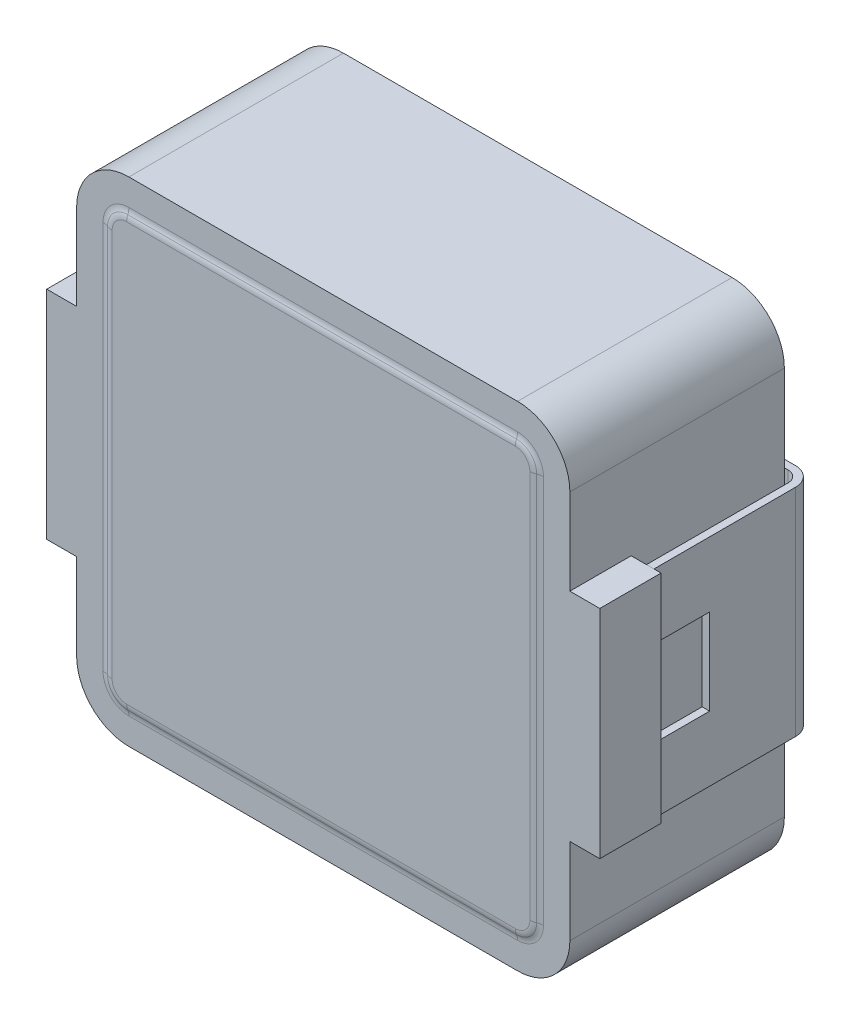
SolidWorks part; units mm, degrees
ref_plane "Front Plane" through (0, 0, 0) normal (0, 0, 1) x (1, 0, 0)
ref_plane "Top Plane" through (0, 0, 0) normal (0, 1, 0) x (1, 0, 0)
ref_plane "Right Plane" through (0, 0, 0) normal (1, 0, 0) x (0, 0, -1)
sketch "Sketch1" plane through (0, 0, 0) normal (0, 0, 1) x (1, 0, 0)
  line L1 (-3.3, 3.3) -> (3.3, 3.3)
  line L2 (-3.3, 3.3) -> (-3.3, -3.3)
  line L3 (-3.3, -3.3) -> (3.3, -3.3)
  line L4 (3.3, 3.3) -> (3.3, -3.3)
  line L5 (-3.3, 3.3) -> (3.3, -3.3) construction
  line L6 (-3.3, -3.3) -> (3.3, 3.3) construction
  point P0 (0, 0)
  dimension "D1" = 6.6
  dimension "D2" = 6.6
extrude "Boss-Extrude1" add sketch "Sketch1" along normal blind 2.9
sketch "Sketch6" plane through (0, 0, 2.9) normal (0, 0, 1) x (1, 0, 0)
  line L1 (-3.7, 1.45) -> (3.7, 1.45)
  line L2 (-3.7, 1.45) -> (-3.7, -1.45)
  line L3 (-3.7, -1.45) -> (3.7, -1.45)
  line L4 (3.7, 1.45) -> (3.7, -1.45)
  line L5 (-3.7, 1.45) -> (3.7, -1.45) construction
  line L6 (-3.7, -1.45) -> (3.7, 1.45) construction
  point P0 (0, 0)
  point P5 (0, 0)
  point P7 (-4.4417, -0.9688)
  dimension "D1" = 7.4
  dimension "D2" = 2.9
extrude "Boss-Extrude5" add sketch "Sketch6" against normal blind 0.85
fillet "Fillet1" radius 0.7 4 edges at (3.3, 3.3, 1.45) (-3.3, 3.3, 1.45) (3.3, -3.3, 1.45) (-3.3, -3.3, 1.45)
sketch "Sketch2" plane through (0, 0, 0) normal (0, 0, -1) x (-1, 0, 0)
  line L0 (3.3, 2.6) -> (3.3, -2.6) construction
  line L1 (3.3, -1.05) -> (2.4, -1.05)
  line L2 (3.3, -1.05) -> (3.3, 1.05)
  line L3 (3.3, 1.05) -> (2.4, 1.05)
  line L4 (2.4, -1.05) -> (2.4, 1.05)
  line L5 (3.3, -1.05) -> (2.4, 1.05) construction
  line L6 (3.3, 1.05) -> (2.4, -1.05) construction
  line L7 (-3.3, -2.6) -> (-3.3, 2.6) construction
  line L8 (-3.3, -1.05) -> (-2.4, -1.05)
  line L9 (-3.3, -1.05) -> (-3.3, 1.05)
  line L10 (-3.3, 1.05) -> (-2.4, 1.05)
  line L11 (-2.4, -1.05) -> (-2.4, 1.05)
  line L12 (-3.3, -1.05) -> (-2.4, 1.05) construction
  line L13 (-3.3, 1.05) -> (-2.4, -1.05) construction
  point P4 (2.85, 0)
  point P11 (-2.85, 0)
  point P14 (2.4, 0)
  point P16 (-2.4, 0)
  dimension "D1" = 0.9
  dimension "D2" = 2.1
extrude "Cut-Extrude1" cut sketch "Sketch2" against normal blind 0.05
sketch "Sketch3" plane through (0, 0, 0.05) normal (0, 0, -1) x (-1, 0, 0)
  line L0 (3.3, -1.05) -> (3.3, 1.05) construction
  line L1 (2.3, -1.445) -> (3.6, -1.445)
  line L2 (2.3, -1.445) -> (2.3, 1.445)
  line L3 (2.3, 1.445) -> (3.6, 1.445)
  line L4 (3.6, -1.445) -> (3.6, 1.445)
  line L5 (2.3, -1.445) -> (3.6, 1.445) construction
  line L6 (2.3, 1.445) -> (3.6, -1.445) construction
  point P4 (2.95, 0)
  dimension "D1" = 1.3
  dimension "D2" = 2.89
  dimension "D3" = 0.3
extrude "Boss-Extrude2" add sketch "Sketch3" along normal blind 0.15
sketch "Sketch4" plane through (0, 0, 0.05) normal (0, 0, 1) x (1, 0, 0)
  line L1 (-3.6, -1.445) -> (-3.3, -1.445)
  line L2 (-3.6, -1.445) -> (-3.6, 1.445)
  line L3 (-3.6, 1.445) -> (-3.3, 1.445)
  line L4 (-3.3, -1.445) -> (-3.3, 1.445)
  line L5 (-3.6, -1.445) -> (-3.3, 1.445) construction
  line L6 (-3.6, 1.445) -> (-3.3, -1.445) construction
  point P4 (-3.45, 0)
extrude "Boss-Extrude3" add sketch "Sketch4" along normal up to surface (2 mm away) up to face at (-3.5, 0, 2.05)
fillet "Fillet2" radius 0.25 1 edges at (-3.6, 0, -0.1)
sketch "Sketch5" plane through (0, 0, 0) normal (0, 0, -1) x (-1, 0, 0)
  line L0 (2.725, -2.7) -> (-2.725, -2.7)
  line L1 (-2.725, -2.7) -> (-2.725, -1.8)
  line L2 (-2.725, -1.8) -> (-1, -1.8)
  line L3 (-1, -1.8) -> (-1, 1.8)
  line L4 (-1, 1.8) -> (-2.725, 1.8)
  line L5 (-2.725, 1.8) -> (-2.725, 2.7)
  line L6 (-2.725, 2.7) -> (2.725, 2.7)
  line L7 (2.725, 2.7) -> (2.725, 1.8)
  line L8 (2.725, 1.8) -> (1, 1.8)
  line L9 (1, 1.8) -> (1, -1.8)
  line L10 (1, -1.8) -> (2.725, -1.8)
  line L11 (2.725, -1.8) -> (2.725, -2.7)
  line L12 (0, -0.4595) -> (0, 0.4595) construction
  line L13 (0.6641, 0) -> (-0.6641, 0) construction
  point P17 (-2.3702, 2.6558)
  point P18 (2.3753, 2.7459)
  point P19 (1.0462, 1.7848)
  dimension "D1" = 5.4
  dimension "D2" = 5.45
  dimension "D3" = 2
  dimension "D4" = 3.6
extrude "Boss-Extrude4" add sketch "Sketch5" along normal blind 0.1
fillet "Fillet3" radius 0.05 12 edges at (0, -2.7, -0.1) (2.725, -2.25, -0.1) (1.8625, -1.8, -0.1) (1, 0, -0.1) (1.8625, 1.8, -0.1) (2.725, 2.25, -0.1) (0, 2.7, -0.1) (-2.725, 2.25, -0.1) (-1.8625, 1.8, -0.1) (-1, 0, -0.1) (-1.8625, -1.8, -0.1) (-2.725, -2.25, -0.1)
fillet "Fillet4" radius 0.05 12 edges at (-1.8625, 1.8, 0) (-2.725, 2.25, 0) (0, 2.7, 0) (2.725, 2.25, 0) (1.8625, 1.8, 0) (1, 0, 0) (1.8625, -1.8, 0) (2.725, -2.25, 0) (0, -2.7, 0) (-1, 0, 0) (-2.725, -2.25, 0) (-1.8625, -1.8, 0)
sketch "Sketch8" plane through (0, 0, 0) normal (0, 0, -1) x (-1, 0, 0)
  line L0 (3.6, 1.445) -> (3.6, -1.445) construction
  line L1 (3.5, -1.445) -> (3.3, -1.445)
  line L2 (3.5, -1.445) -> (3.5, 1.445)
  line L3 (3.5, 1.445) -> (3.3, 1.445)
  line L4 (3.3, -1.445) -> (3.3, 1.445)
  line L5 (3.5, -1.445) -> (3.3, 1.445) construction
  line L6 (3.5, 1.445) -> (3.3, -1.445) construction
  point P4 (3.4, 0)
  point P5 (0, 0)
  point P7 (0, 0)
  dimension "D1" = 0.1
extrude "Cut-Extrude2" cut sketch "Sketch8" against normal up to surface (2.05 mm away) up to face at (-3.475, 0, 2.05)
fillet "Fillet5" radius 0.15 1 edges at (-3.5, 0, 0)
sketch "Sketch9" plane through (-3.6, 0, 0) normal (-1, 0, 0) x (0, 0, 1)
  line L0 (2.05, 1.445) -> (2.05, -1.445) construction
  line L1 (2.05, 0.575) -> (1.3, 0.575)
  line L2 (2.05, 0.575) -> (2.05, -0.575)
  line L3 (2.05, -0.575) -> (1.3, -0.575)
  line L4 (1.3, 0.575) -> (1.3, -0.575)
  line L5 (2.05, 0.575) -> (1.3, -0.575) construction
  line L6 (2.05, -0.575) -> (1.3, 0.575) construction
  point P4 (1.675, 0)
  point P7 (0, 0)
  dimension "D1" = 1.15
  dimension "D2" = 0.75
extrude "Cut-Extrude3" cut sketch "Sketch9" against normal up to surface (0.1 mm away) up to face at (-3.5, 0, 1.1)
mirror "Mirror2" about plane through (0, 0, 0) normal (1, 0, 0) of "Fillet5", "Boss-Extrude3", "Boss-Extrude2", "Fillet2", "Cut-Extrude2", "Cut-Extrude3"
sketch "Sketch10" plane through (0, 0, 2.9) normal (0, 0, 1) x (1, 0, 0)
  line L0 (2.6, 3.3) -> (-2.6, 3.3) construction
  line L1 (-2.6, 2.9) -> (2.6, 2.9)
  line L2 (-2.9, 2.6) -> (-2.9, -2.6)
  line L3 (-2.6, -2.9) -> (2.6, -2.9)
  line L4 (2.9, 2.6) -> (2.9, -2.6)
  line L5 (-2.6661, -2.19) -> (3.6721, 3.0164) construction
  line L6 (4.5434, -2.7178) -> (-1.7923, 1.0721) construction
  line L8 (-4.497, 5.4132) -> (5.503, 5.4132)
  line L9 (-4.497, 5.4132) -> (-4.497, -4.5868)
  line L10 (-4.497, -4.5868) -> (5.503, -4.5868)
  line L11 (5.503, 5.4132) -> (5.503, -4.5868)
  line L12 (-4.497, 5.4132) -> (5.503, -4.5868) construction
  line L13 (-4.497, -4.5868) -> (5.503, 5.4132) construction
  arc A0 (-2.9, 2.6) -> (-2.6, 2.9) centre (-2.6, 2.6) cw
  arc A1 (2.6, 2.9) -> (2.9, 2.6) centre (2.6, 2.6) cw
  arc A2 (2.9, -2.6) -> (2.6, -2.9) centre (2.6, -2.6) cw
  arc A3 (-2.6, -2.9) -> (-2.9, -2.6) centre (-2.6, -2.6) cw
  arc A4 (-2.6, 3.3) -> (-3.3, 2.6) centre (-2.6, 2.6) ccw construction
  point P0 (0, 0)
  point P20 (-2.8121, 2.8121)
  point P24 (-3.095, 3.095)
  point P25 (0.503, 0.4132)
  dimension "D1" = 5.8
  dimension "D2" = 5.8
  dimension "D3" = 0.4
  dimension "D4" = 0.4
  dimension "D5" = 10
extrude "Cut-Extrude4" cut sketch "Sketch10" against normal blind 0.03
fillet "Fillet6" radius 0.2 8 edges at (-2.8121, -2.8121, 2.9) (-2.9, 0, 2.9) (-2.8121, 2.8121, 2.9) (0, 2.9, 2.9) (2.8121, 2.8121, 2.9) (2.9, 0, 2.9) (2.8121, -2.8121, 2.9) (0, -2.9, 2.9)
fillet "Fillet7" radius 0.2 8 edges at (-2.8121, -2.8121, 2.87) (-2.9, 0, 2.87) (-2.8121, 2.8121, 2.87) (0, 2.9, 2.87) (2.8121, 2.8121, 2.87) (2.9, 0, 2.87) (2.8121, -2.8121, 2.87) (0, -2.9, 2.87)
equation "\"D4@Sketch10\"=\"D3@Sketch10\""
